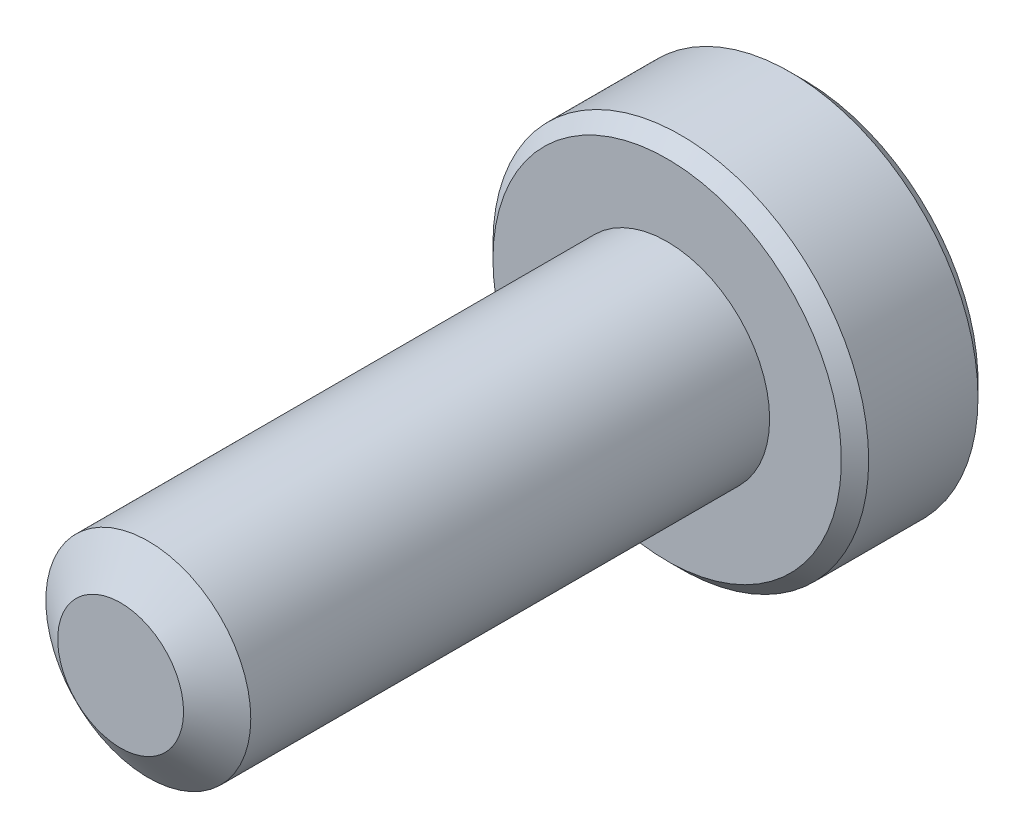
SolidWorks part; units mm, degrees
ref_plane "Front Plane" through (0, 0, 0) normal (0, 0, 1) x (1, 0, 0)
ref_plane "Top Plane" through (0, 0, 0) normal (0, 1, 0) x (1, 0, 0)
ref_plane "Right Plane" through (0, 0, 0) normal (1, 0, 0) x (0, 0, -1)
sketch "Sketch1" plane through (0, 0, 0) normal (0, 0, 1) x (1, 0, 0)
  circle A0 centre (0, 0) radius 1.5
  dimension "OD" = 3
extrude "Extrude1" add sketch "Sketch1" against normal blind 8
sketch "Sketch2" plane through (0, 0, 0) normal (0, 0, 1) x (1, 0, 0)
  circle A0 centre (0, 0) radius 1.5 construction
  circle A1 centre (0, 0) radius 1.5
curve "Helix/Spiral1" pitch 0.5 height 8.5 turns 17 parameters "pitch"=0.5
sketch "Sketch3" plane through (0, 0, 0) normal (1, 0, 0) x (0, 0, -1)
  line L0 (-0.4375, 1.5) -> (-0.25, 1.1752)
  line L1 (-0.25, 1.1752) -> (-0.1875, 1.1752)
  line L2 (-0.1875, 1.1752) -> (0, 1.5)
  line L3 (-0.4375, 1.5) -> (0, 1.5)
  line L4 (-0.2187, 1.5) -> (-0.2187, 1.1752) construction
  line L5 (-0.3437, 1.3376) -> (-0.0937, 1.3376) construction
  line L6 (0, 1.5) -> (0, -1.5) construction
  dimension "D1" = 0.0625
  dimension "D2" = 0.25
  dimension "D3" = 60
sweep "Cut-Sweep1" [suppressed] cut profiles "Sketch3" path "Helix/Spiral1"
sketch "Sketch4" plane through (0, 0, 0) normal (1, 0, 0) x (0, 0, -1)
  line L0 (0.4053, 1.5) -> (0, 0.9212)
  line L1 (0, 0.9212) -> (0, 1.5)
  line L2 (0.4053, 1.5) -> (0, 1.5)
  line L3 (-0.4375, 1.5) -> (0, 1.5) construction
  line L4 (0, 0) -> (7.0209, 0) construction
  dimension "D1" = 55
  dimension "D2" = 0.254
revolve "Cut-Revolve1" cut sketch "Sketch4" angle 360 about L4
sketch "Sketch6" plane through (0, 0, -8) normal (0, 0, -1) x (-1, 0, 0)
  circle A0 centre (0, 0) radius 2.75
  dimension "head dia" = 5.5
extrude "Extrude2" add sketch "Sketch6" along normal blind 2
sketch "Sketch5" plane through (0, 0, 0) normal (1, 0, 0) x (0, 0, -1)
  line L1 (8, 1.5) -> (18.1202, 1.5)
  line L2 (8, 1.5) -> (8, 0)
  line L3 (8, 0) -> (18, 0)
  line L4 (18, 1.1698) -> (18, 0)
  line L5 (18.1202, 1.5) -> (18, 1.1698)
  line L6 (0, 0) -> (9.9695, 0) construction
  line L7 (8, 2.75) -> (8, -2.75) construction
  point P3 (18, 1.5)
  point P10 (18, 1.5)
  dimension "D1" = 0.3302
  dimension "Thread min" = 18
  dimension "D2" = 1.5
  dimension "D3" = 20
revolve "partially thread" [suppressed] add sketch "Sketch5" angle 360 about L6
sketch "Sketch7" plane through (0, 0, -10) normal (0, 0, -1) x (-1, 0, 0)
  line L1 (0, 1.1547) -> (-1, 0.5774)
  line L2 (-1, 0.5774) -> (-1, -0.5774)
  line L3 (-1, -0.5774) -> (0, -1.1547)
  line L4 (0, -1.1547) -> (1, -0.5774)
  line L5 (1, -0.5774) -> (1, 0.5774)
  line L6 (1, 0.5774) -> (0, 1.1547)
  circle A0 centre (0, 0) radius 1 construction
  dimension "hex dia" = 2
extrude "Cut-Extrude1" cut sketch "Sketch7" against normal blind 1.5
sketch "Sketch8" plane through (0, 0, -10) normal (0, 0, -1) x (-1, 0, 0)
  circle A0 centre (0, 0) radius 1.1547
extrude "Cut-Extrude2" cut sketch "Sketch8" against normal through all draft 45
chamfer "Chamfer1" distance 0.2 angle 45 2 edges at (-2.75, 0, -10) (-2.75, 0, -8)
sketch "Sketch9" plane through (0, 0, 0) normal (1, 0, 0) x (0, 0, -1)
  line L0 (0, 1.5) -> (0, -1.5) construction
  line L1 (2.75, 1.5) -> (2.75, -1.5) construction
  dimension "D1" = 2.75
equation "\"D3@Helix/Spiral1\" = \"screw length@Extrude1\"+\"pitch@Helix/Spiral1\""
equation "\"D1@Sketch3\" = \"pitch@Helix/Spiral1\"*.125"
equation "\"D2@Sketch3\" = \"pitch@Helix/Spiral1\"*.5"
equation "\"D1@Cut-Extrude1\" = \"hex dia@Sketch7\"*.75"
equation "\"D1@Chamfer1\" = \"head depth@Extrude2\"*.1"
equation "\"D1@Sketch9\" = \"pitch@Helix/Spiral1\"*5.5"
equation "\"D2@Sketch5\" = \"OD@Sketch1\"/2"
